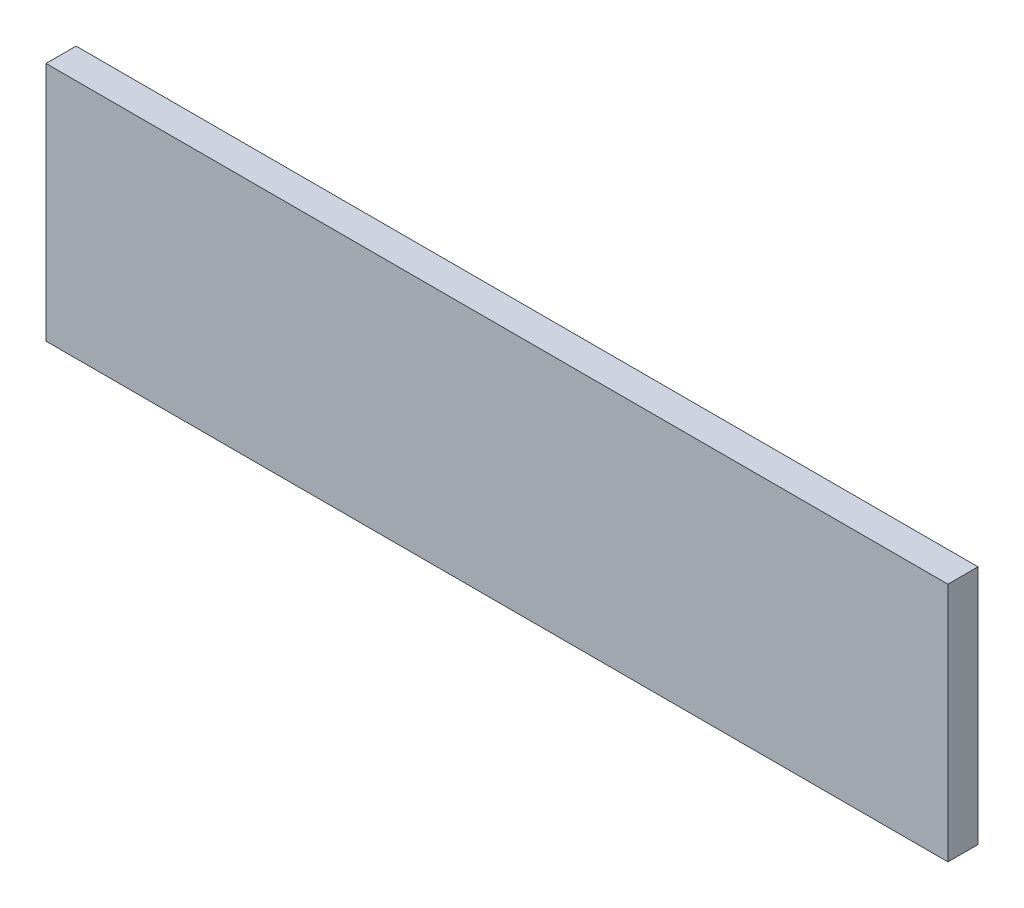
SolidWorks part; units mm, degrees
ref_plane "正面" through (0, 0, 0) normal (0, 0, 1) x (1, 0, 0)
ref_plane "平面" through (0, 0, 0) normal (0, 1, 0) x (1, 0, 0)
ref_plane "右側面" through (0, 0, 0) normal (1, 0, 0) x (0, 0, -1)
sketch "ｽｹｯﾁ1" plane through (0, 0, 0) normal (0, 0, 1) x (1, 0, 0)
  line L1 (-75, 20) -> (75, 20)
  line L2 (-75, 20) -> (-75, -20)
  line L3 (-75, -20) -> (75, -20)
  line L4 (75, 20) -> (75, -20)
  line L5 (-75, 20) -> (75, -20) construction
  line L6 (-75, -20) -> (75, 20) construction
  point P0 (0, 0)
  dimension "D1" = 40
  dimension "D2" = 150
extrude "ﾎﾞｽ - 押し出し1" add sketch "ｽｹｯﾁ1" along normal blind 5
